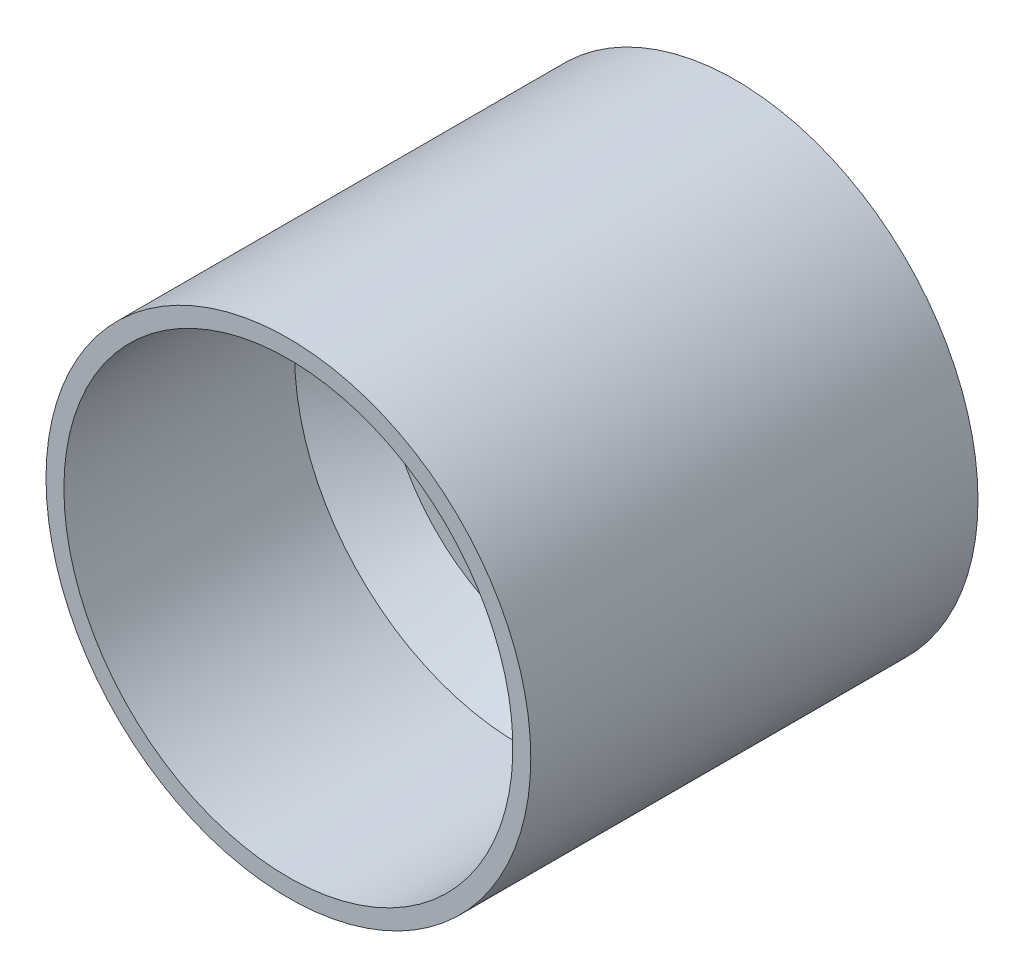
SolidWorks part; units mm, degrees
material "ABS"
ref_plane "Front Plane" through (0, 0, 0) normal (0, 0, 1) x (1, 0, 0)
ref_plane "Top Plane" through (0, 0, 0) normal (0, 1, 0) x (1, 0, 0)
ref_plane "Right Plane" through (0, 0, 0) normal (1, 0, 0) x (0, 0, -1)
sketch "Sketch1" plane through (0, 0, 0) normal (0, 1, 0) x (1, 0, 0)
  line L0 (0, 51.2882) -> (0, -69.4276) construction
  line L1 (15.25, 26.5) -> (15.25, 23.5)
  line L2 (15.25, 23.5) -> (25.1, 23.5)
  line L3 (25.1, 23.5) -> (25.1, -23.5)
  line L4 (25.1, -23.5) -> (27.1, -23.5)
  line L5 (27.1, -23.5) -> (27.1, 26.5)
  line L6 (27.1, 26.5) -> (15.25, 26.5)
  point P9 (25.1, 0)
  dimension "D1" = 30.5
  dimension "D2" = 3
  dimension "D3" = 2
  dimension "D4" = 50.2
  dimension "D6" = 50
revolve "Revolve1" add sketch "Sketch1" angle 360 about L0
sketch "Sketch2" plane through (0, 0, -26.5) normal (0, 0, -1) x (-1, 0, 0)
  circle A0 centre (0, 0) radius 20.25 construction
  circle A1 centre (0, 20.25) radius 2
  circle A2 centre (17.537, -10.125) radius 2
  circle A3 centre (-17.537, -10.125) radius 2
  point P12 (0, 0)
  dimension "D1" = 40.5
  dimension "D2" = 4
  dimension "D3" = 3
extrude "Cut-Extrude1" cut sketch "Sketch2" against normal blind 10 contours A0 | A0 | A0 | A0 | A0 A1 | A0 A1 | A3 | A2 region at (0, 20.25, -26.5)
sketch "Sketch3" plane through (0, 0, 0) normal (0, 1, 0) x (1, 0, 0)
  line L0 (25.1, 10.3) -> (0, 10.3)
  line L1 (25.1, 23.5) -> (25.1, -23.5) construction
  line L2 (27.1, 26.5) -> (15.25, 26.5) construction
  line L3 (0, 10.3) -> (0, 7.3)
  line L4 (0, 7.3) -> (25.1, 7.3)
  line L5 (25.1, 7.3) -> (25.1, 10.3)
  line L6 (0, 51.2882) -> (0, -69.4276) construction
  dimension "D1" = 3
  dimension "D2" = 16.2
revolve "Revolve2" add sketch "Sketch3" angle 360 about L0
chamfer "Chamfer1" distance 5 angle 45 2 edges at (-25.1, 0, -7.3) (25.1, 0, -10.3)
sketch "Sketch4" plane through (0, 0, -10.3) normal (0, 0, -1) x (-1, 0, 0)
  line L0 (-6.05, 3.6194) -> (-6.05, -3.6194)
  line L1 (6.05, -3.6194) -> (6.05, 3.6194)
  line L2 (0, 15.25) -> (0, -15.25) construction
  line L3 (0, 0) -> (0, -84.6003) construction
  line L4 (-25.1, 0) -> (-27.1, 0) construction
  line L5 (-6.364, 6.364) -> (6.364, 6.364) construction
  circle A0 centre (0, 0) radius 9 construction
  arc A1 (-6.05, -3.6194) -> (6.05, -3.6194) centre (0, 0) ccw
  arc A2 (6.05, 3.6194) -> (-6.05, 3.6194) centre (0, 0) ccw
  circle A3 centre (-6.364, 6.364) radius 1.1
  circle A4 centre (6.364, 6.364) radius 1.1
  circle A5 centre (6.364, -6.364) radius 1.1
  circle A6 centre (-6.364, -6.364) radius 1.1
  circle A7 centre (0, 0) radius 15.25 construction
  circle A8 centre (0, 12.5) radius 1.5
  circle A9 centre (0, -12.5) radius 1.5
  circle A10 centre (0, 0) radius 11 construction
  point P21 (0, 0)
  dimension "D1" = 18
  dimension "D2" = 14.1
  dimension "D5" = 2.2
  dimension "D7" = 3
  dimension "D8" = 3
  dimension "D12" = 22
  dimension "D3" = 12.1
  dimension "D4" = 12.1
  dimension "D9" = 12.5
  dimension "D10" = 12.5
  dimension "D11" = 0
  dimension "D6" = 4
extrude "Cut-Extrude2" cut sketch "Sketch4" against normal blind 10
